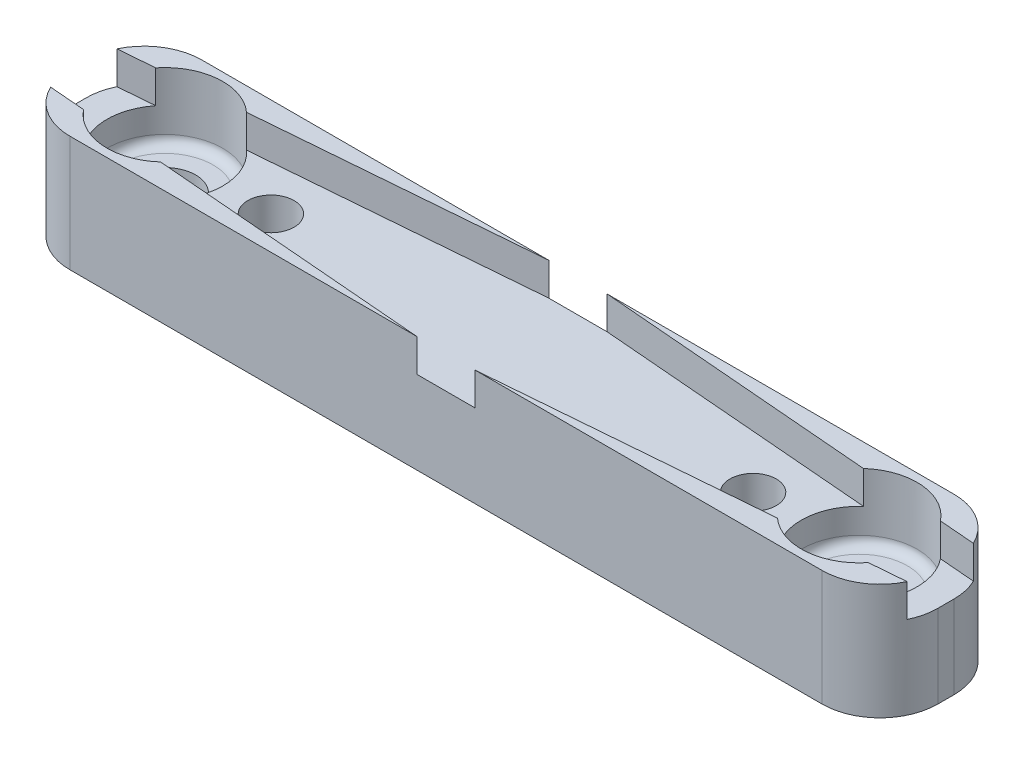
SolidWorks part; units mm, degrees
ref_plane "前视基准面" through (0, 0, 0) normal (0, 0, 1) x (1, 0, 0)
ref_plane "上视基准面" through (0, 0, 0) normal (0, 1, 0) x (1, 0, 0)
ref_plane "右视基准面" through (0, 0, 0) normal (1, 0, 0) x (0, 0, -1)
sketch "草图2" plane through (0, 0, 4.5) normal (0, 1, 0) x (1, 0, 0)
  line L11 (22.5, -3.4214) -> (22.5, 3.4214)
  line L12 (-3.9065, -3.4214) -> (3.9065, -3.4214)
  line L13 (22.5, 3.4214) -> (3.9065, 3.4214)
  line L14 (-22.5, -3.4214) -> (-22.5, 3.4214)
  line L15 (-3.9065, 3.4214) -> (3.9065, 3.4214)
  line L16 (22.5, -3.4214) -> (-22.5, 3.4214) construction
  line L17 (22.5, -3.4214) -> (3.9065, -3.4214)
  line L18 (-3.9065, -3.4214) -> (-22.5, -3.4214)
  line L19 (0, 0) -> (0, 12.7469) construction
  line L20 (-3.9065, 3.4214) -> (-22.5, 3.4214)
  line L21 (22.5, 3.4214) -> (-22.5, -3.4214) construction
  circle A2 centre (-12.5, 0) radius 1.2
  circle A3 centre (12.5, 0) radius 1.2
  circle A4 centre (-18, 0) radius 1.6
  circle A5 centre (18, 0) radius 1.6
  point P17 (0, 0)
extrude "凸台-拉伸2" add sketch "草图2" along normal blind 6
sketch "草图3" plane through (0, 0, 0) normal (0, -1, 0) x (-1, 0, 0)
  line L1 (0, 0) -> (0, 10.9531) construction
  circle A2 centre (-12.5, -4.5) radius 3
  circle A3 centre (12.5, -4.5) radius 3
extrude "切除-拉伸1" cut sketch "草图3" against normal blind 1
fillet "圆角2" radius 3 4 edges at (22.5, 3, 1.0786) (22.5, 3, 7.9214) (-22.5, 3, 7.9214) (-22.5, 3, 1.0786)
sketch "草图4" plane through (0, 6, 0) normal (0, 1, 0) x (1, 0, 0)
  line L8 (43.0791, -4.5) -> (0, -8.0462)
  line L9 (-43.0791, -4.5) -> (0, -0.9538)
  line L10 (17.5, -4.5) -> (7.0116, -4.5) construction
  line L11 (0, -0.9538) -> (43.0791, -4.5)
  line L12 (0, -4.5) -> (43.0791, -4.5) construction
  line L13 (0, -8.0462) -> (-43.0791, -4.5)
  line L14 (0, -4.5) -> (0, -9.0689) construction
extrude "切除-拉伸2" cut sketch "草图4" against normal blind 1.7
sketch "草图5" plane through (0, 4.3, 0) normal (0, 1, 0) x (1, 0, 0)
  circle A0 centre (-18, -4.5) radius 3
  circle A1 centre (18, -4.5) radius 3
extrude "切除-拉伸3" cut sketch "草图5" against normal blind 1.8 and the other way through all
fillet "圆角3" radius 0.5 4 edges at (18, 2.5, 7.5) (-18, 2.5, 7.5) (-12.5, 1, 7.5) (12.5, 1, 1.5)
